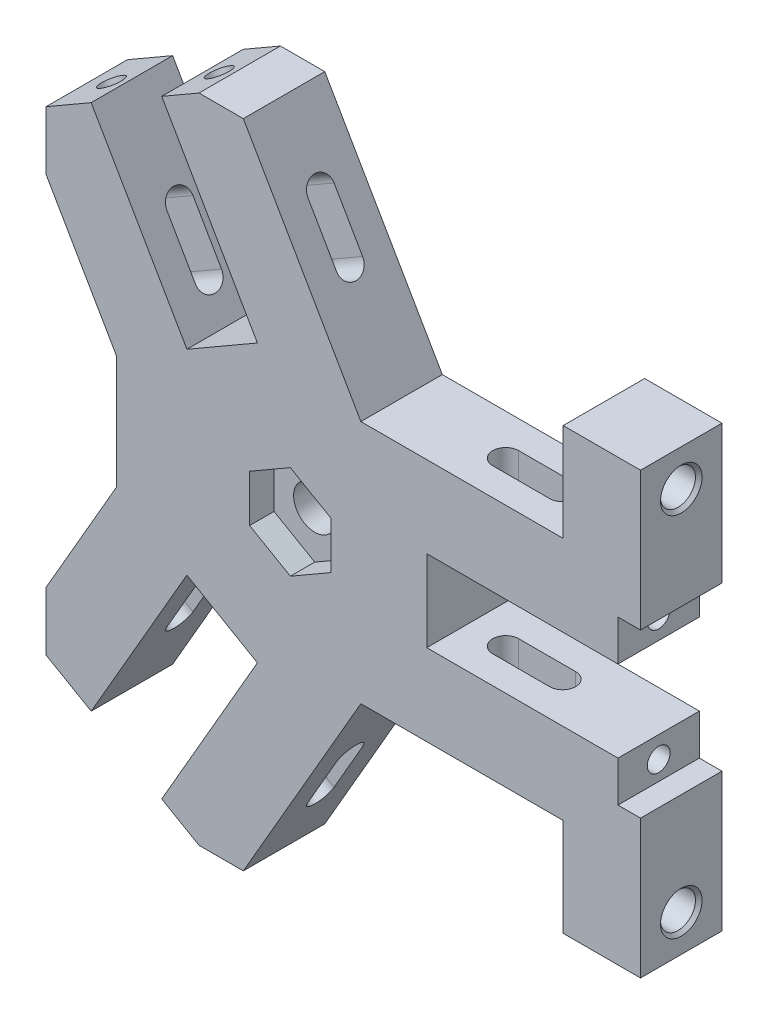
SolidWorks part; units mm, degrees
ref_plane "Front" through (0, 0, 0) normal (0, 0, 1) x (1, 0, 0)
ref_plane "Top" through (0, 0, 0) normal (0, 1, 0) x (1, 0, 0)
ref_plane "Right" through (0, 0, 0) normal (1, 0, 0) x (0, 0, -1)
sketch "Sketch1" plane through (0, 0, 0) normal (0, 0, 1) x (1, 0, 0)
  line L1 (0, 0) -> (73, 0)
  line L2 (0, 0) -> (0, 80)
  line L3 (0, 80) -> (73, 80)
  line L4 (73, 0) -> (73, 80)
  dimension "D1" = 80
  dimension "D2" = 73
extrude "Boss-Extrude1" add sketch "Sketch1" along normal blind 10
sketch "Sketch2" plane through (0, 0, 10) normal (0, 0, 1) x (1, 0, 0)
  line L1 (0, 80) -> (0, 0) construction
  line L2 (18.75, 59.4856) -> (18.75, 20.5144) construction
  line L3 (18.75, 20.5144) -> (52.5, 40) construction
  line L4 (52.5, 40) -> (18.75, 59.4856) construction
  circle A0 centre (30, 40) radius 22.5 construction
  point P3 (0, 40)
  dimension "D1" = 22.5
  dimension "D3" = 30
ref_axis "Axis1" through (30, 40, 10) along (0, 0, -1)
sketch "Sketch3" plane through (0, 0, 10) normal (0, 0, 1) x (1, 0, 0)
  line L0 (25.9551, 57.0059) -> (17.2949, 52.0059)
  line L1 (25.9551, 57.0059) -> (20.2051, 66.9652)
  line L2 (17.2949, 52.0059) -> (11.5449, 61.9652)
  line L3 (20.2051, 66.9652) -> (11.5449, 61.9652)
  line L4 (25.9551, 57.0059) -> (11.5449, 61.9652) construction
  line L5 (17.2949, 52.0059) -> (20.2051, 66.9652) construction
  line L6 (11.5449, 18.0348) -> (20.2051, 13.0348)
  line L7 (11.5449, 18.0348) -> (17.2949, 27.9941)
  line L8 (20.2051, 13.0348) -> (25.9551, 22.9941)
  line L9 (17.2949, 27.9941) -> (25.9551, 22.9941)
  line L10 (11.5449, 18.0348) -> (25.9551, 22.9941) construction
  line L11 (20.2051, 13.0348) -> (17.2949, 27.9941) construction
  line L13 (46.75, 45) -> (58.25, 45)
  line L14 (46.75, 45) -> (46.75, 35)
  line L15 (46.75, 35) -> (58.25, 35)
  line L16 (58.25, 45) -> (58.25, 35)
  line L17 (46.75, 45) -> (58.25, 35) construction
  line L18 (46.75, 35) -> (58.25, 45) construction
  point P0 (52.5, 40)
  point P1 (18.75, 59.4856)
  point P2 (18.75, 20.5144)
  dimension "D1" = 60
  dimension "D2" = 60
  dimension "D3" = 10
  dimension "D4" = 10
  dimension "D5" = 10
  dimension "D6" = 11.5
  dimension "D7" = 11.5
  dimension "D8" = 11.5
extrude "Cut-Extrude1" cut sketch "Sketch3" against normal blind 10
sketch "Sketch4" plane through (0, 45, 0) normal (0, -1, 0) x (1, 0, 0)
  line L0 (52.5, 7.2) -> (73, 7.2)
  line L1 (73, 10) -> (73, 0) construction
  line L2 (73, 7.2) -> (73, 2.8)
  line L3 (73, 2.8) -> (52.5, 2.8)
  line L4 (58.25, 10) -> (46.75, 10) construction
  arc A0 (52.5, 2.8) -> (52.5, 7.2) centre (52.5, 5) cw
  point P10 (52.5, 10)
  dimension "D1" = 2.2
  dimension "D2" = 5
sketch "Sketch5" plane through (0, 0, 10) normal (0, 0, 1) x (1, 0, 0)
  line L1 (58.25, 45) -> (85.6587, 45)
  line L2 (58.25, 45) -> (58.25, 35)
  line L3 (58.25, 35) -> (85.6587, 35)
  line L4 (85.6587, 45) -> (85.6587, 35)
extrude "Cut-Extrude3" cut sketch "Sketch5" against normal blind 10
sketch "Sketch6" plane through (9.5096, -5.4904, 0) normal (-0.866, 0.5, 0) x (0, 0, 1)
  line L0 (2.8, 27.141) -> (2.8, -15.6837)
  line L1 (2.8, -15.6837) -> (7.2, -15.6837)
  line L2 (7.2, -15.6837) -> (7.2, 27.141)
  line L3 (10, 21.391) -> (10, 32.891) construction
  arc A0 (2.8, 27.141) -> (7.2, 27.141) centre (5, 27.141) cw
  point P8 (10, 27.141)
  dimension "D1" = 2.2
  dimension "D2" = 5
  dimension "D3" = 4.4
pattern_circular "CirPattern1" count 3 over 360 about axis through (30, 40, 10) along (0, 0, -1) of "Cut-Extrude3"
ref_plane "Plane1" through (39.8205, 22.9904, 0) normal (0.866, 0.5, 0) x (0, 0, -1)
ref_plane "Plane2" through (5.1795, -2.9904, 0) normal (-0.866, 0.5, 0) x (0, 0, -1)
sketch "Sketch7" plane through (44.1506, 25.4904, 0) normal (-0.866, -0.5, 0) x (0, 0, 1)
  line L0 (2.8, 42.141) -> (2.8, 92.141)
  line L1 (2.8, 92.141) -> (7.2, 92.141)
  line L2 (7.2, 92.141) -> (7.2, 42.141)
  line L3 (10, 36.391) -> (10, 62.9423) construction
  arc A0 (2.8, 42.141) -> (7.2, 42.141) centre (5, 42.141) ccw
  dimension "D1" = 2.2
  dimension "D2" = 5
  dimension "D3" = 4.4
  dimension "D4" = 50
hole_wizard "M6 Clearance Hole1" positions "Sketch8" profile "Sketch9" hole size "M6" standard "ISO" end condition through all
sketch "Sketch8" plane through (0, 0, 10) normal (0, 0, 1) x (1, 0, 0)
  point P0 (30, 40)
sketch "Sketch9" plane through (30, 40, 10) normal (1, 0, 0) x (0, -1, 0)
  line L0 (0, 0) -> (0, 10)
  line L1 (0, 10) -> (2.6, 10)
  line L2 (2.6, 10) -> (2.6, 0)
  line L5 (2.6, 0) -> (0, 0)
  line L11 (0, -6.35) -> (0, 107.95) construction
  dimension "Thru Hole Dia." = 5.2
  dimension "Thru Hole Depth" = 10
sketch "Sketch10" plane through (0, 0, 10) normal (0, 0, 1) x (1, 0, 0)
  line L0 (17.2949, 52.0059) -> (25.9551, 57.0059) construction
  line L1 (30, 45.7735) -> (25, 42.8868)
  line L2 (25, 42.8868) -> (25, 37.1132)
  line L3 (25, 37.1132) -> (30, 34.2265)
  line L4 (30, 34.2265) -> (35, 37.1132)
  line L5 (35, 37.1132) -> (35, 42.8868)
  line L6 (35, 42.8868) -> (30, 45.7735)
  circle A0 centre (30, 40) radius 5 construction
  dimension "D1" = 10
extrude "Cut-Extrude6" cut sketch "Sketch10" against normal blind 3
ref_axis "Axis2" through (30, 40, 0) along (0, 0, 1)
ref_plane "Plane4" through (30, 0, 0) normal (-1, 0, 0) x (0, 0, 1)
sketch "Sketch11" plane through (0, 0, 0) normal (0, -1, 0) x (1, 0, 0)
  line L0 (73, 10) -> (73, 0) construction
  line L1 (51.44, 6.6) -> (58.44, 6.6)
  line L2 (51.44, 3.4) -> (58.44, 3.4)
  line L3 (12.6795, 10) -> (73, 10) construction
  arc A1 (51.44, 6.6) -> (51.44, 3.4) centre (51.44, 5) ccw
  arc A2 (58.44, 6.6) -> (58.44, 3.4) centre (58.44, 5) cw
  dimension "D1" = 1.6
  dimension "D4" = 5
  dimension "D2" = 7
  dimension "D3" = 14.56
extrude "Cut-Extrude7" cut sketch "Sketch11" against normal through all
pattern_circular "CirPattern2" count 3 over 360 about axis through (30, 40, 7) along (0, 0, -1) of "Cut-Extrude7"
sketch "Sketch12" plane through (0, 0, 10) normal (0, 0, 1) x (1, 0, 0)
  line L0 (73, 0) -> (73, 25)
  line L1 (73, 0) -> (73, 35) construction
  line L2 (73, 25) -> (38.6603, 25)
  line L3 (38.6603, 25) -> (24.2265, 0)
  line L4 (12.6795, 0) -> (73, 0) construction
  line L5 (24.2265, 0) -> (73, 0)
  line L6 (12.6795, 0) -> (25.9551, 22.9941) construction
  line L8 (46.75, 35) -> (73, 35) construction
  dimension "D1" = 10
  dimension "D2" = 10
extrude "Cut-Extrude8" cut sketch "Sketch12" against normal blind 10
ref_plane "Plane3" through (0, 40, 0) normal (0, -1, 0) x (-1, 0, 0)
mirror "Mirror1" about plane through (0, 40, 0) normal (0, -1, 0) of "Cut-Extrude8"
sketch "Sketch13" plane through (0, 0, 10) normal (0, 0, 1) x (1, 0, 0)
  line L0 (0, 61.9615) -> (8.6244, 47.0237)
  line L1 (0, 80) -> (0, 0) construction
  line L2 (8.6244, 47.0237) -> (8.6244, 32.9763)
  line L3 (8.6244, 32.9763) -> (0, 18.0385)
  line L4 (0, 18.0385) -> (0, 61.9615)
  line L5 (1.1325, 80) -> (17.2949, 52.0059) construction
  line L6 (17.2949, 27.9941) -> (1.1325, 0) construction
  circle A0 centre (30, 40) radius 22.5 construction
  dimension "D1" = 10
extrude "Cut-Extrude9" cut sketch "Sketch13" against normal blind 10
sketch "Sketch14" plane through (0, 0, 10) normal (0, 0, 1) x (1, 0, 0)
  line L0 (-3.1154, 12.6425) -> (22.8654, -2.3575)
  line L1 (22.8654, -2.3575) -> (18.1699, -10.4904)
  line L2 (18.1699, -10.4904) -> (-7.8109, 4.5096)
  line L3 (-7.8109, 4.5096) -> (-3.1154, 12.6425)
  line L4 (25.9551, 22.9941) -> (17.2949, 27.9941) construction
  line L5 (38.6603, 25) -> (24.2265, 0) construction
  line L6 (0, 18.0385) -> (8.6244, 32.9763) construction
  dimension "D1" = 23.5
extrude "Cut-Extrude10" cut sketch "Sketch14" against normal blind 10
mirror "Mirror2" about plane through (0, 40, 0) normal (0, -1, 0) of "Cut-Extrude10"
sketch "Sketch15" plane through (0, 0, 10) normal (0, 0, 1) x (1, 0, 0)
  line L0 (73, 45) -> (73, 55) construction
  line L1 (73, 19) -> (182, 19)
  line L2 (73, 19) -> (73, 61)
  line L3 (73, 61) -> (182, 61)
  line L4 (182, 19) -> (182, 61)
  line L5 (0, 0) -> (0, 81.4596) construction
  point P6 (73, 40)
  dimension "D1" = 42
  dimension "D2" = 182
extrude "Boss-Extrude2" add sketch "Sketch15" against normal blind 10
sketch "Sketch16" plane through (0, 0, 10) normal (0, 0, 1) x (1, 0, 0)
  line L1 (73, 50.5) -> (98, 50.5)
  line L2 (73, 50.5) -> (73, 29.5)
  line L3 (73, 29.5) -> (98, 29.5)
  line L4 (98, 50.5) -> (98, 29.5)
  line L5 (73, 45) -> (73, 35) construction
  line L7 (182, 61) -> (73, 61) construction
  dimension "D1" = 25
  dimension "D2" = 21
  dimension "D3" = 10.5
sketch "Sketch18" plane through (0, 0, 10) normal (0, 0, 1) x (1, 0, 0)
  line L0 (182, 61) -> (73, 61) construction
  line L1 (113.8, 24.5) -> (82.8, 24.5)
  line L2 (113.8, 24.5) -> (113.8, 55.5)
  line L3 (113.8, 55.5) -> (82.8, 55.5)
  line L4 (82.8, 24.5) -> (82.8, 55.5)
  line L5 (113.8, 24.5) -> (82.8, 55.5) construction
  line L6 (113.8, 55.5) -> (82.8, 24.5) construction
  line L7 (73, 61) -> (73, 55) construction
  point P0 (98.3, 40)
  dimension "D1" = 31
  dimension "D2" = 31
  dimension "D3" = 68.3
  dimension "D4" = 5.5
  dimension "D5" = 9.8
sketch "Sketch21" plane through (0, 0, 10) normal (0, 0, 1) x (1, 0, 0)
  line L4 (97.55, 40) -> (99.05, 40) construction
  line L5 (113.8, 24.5) -> (82.8, 55.5) construction
  line L6 (97.55, 47.5) -> (99.05, 47.5)
  line L7 (97.55, 32.5) -> (99.05, 32.5)
  arc A2 (97.55, 47.5) -> (97.55, 32.5) centre (97.55, 40) ccw
  arc A3 (99.05, 32.5) -> (99.05, 47.5) centre (99.05, 40) ccw
  point P5 (98.3, 40)
  dimension "D1" = 15
  dimension "D2" = 1.5
sketch "Sketch22" plane through (0, 0, 10) normal (0, 0, 1) x (1, 0, 0)
  line L0 (182, 19) -> (182, 61) construction
  line L1 (182, 67) -> (167, 67)
  line L2 (182, 67) -> (182, 13)
  line L3 (182, 13) -> (167, 13)
  line L4 (167, 67) -> (167, 13)
  point P6 (182, 40)
  dimension "D1" = 15
  dimension "D2" = 54
extrude "Boss-Extrude3" add sketch "Sketch22" against normal blind 10
sketch "Sketch23" plane through (182, 0, 0) normal (1, 0, 0) x (0, 0, -1)
  line L0 (-5, 62.5) -> (-5, 17.5) construction
  point P2 (-5, 40)
  dimension "D1" = 45
  dimension "D2" = 5
hole_wizard "M4 Clearance Hole1" positions "Sketch24" profile "Sketch25" hole size "M4" standard "DIN"
sketch "Sketch24" plane through (182, 0, 0) normal (1, 0, 0) x (0, 0, -1)
  point P0 (-5, 62.5)
  point P3 (-5, 17.5)
sketch "Sketch25" plane through (182, 62.5, 5) normal (0, 1, 0) x (0, 0, -1)
  line L0 (0, 0) -> (0, 31.3519)
  line L1 (0, 31.3519) -> (2.25, 30)
  line L2 (2.25, 30) -> (2.25, 0)
  line L5 (2.25, 0) -> (0, 0)
  line L10 (0, 31.3519) -> (-2.25, 30) construction
  line L11 (0, -6.35) -> (0, 107.95) construction
  dimension "Hole Dia." = 4.5
  dimension "Hole Depth" = 30
  dimension "Drill Angle" = 118
sketch "Sketch26" plane through (0, 0, 10) normal (0, 0, 1) x (1, 0, 0)
  line L0 (119.3, 61) -> (119.3, 55)
  line L1 (167, 61) -> (73, 61) construction
  line L2 (119.3, 55) -> (167, 55)
  line L3 (167, 55) -> (167, 61)
  line L4 (167, 61) -> (119.3, 61)
  dimension "D1" = 5.5
  dimension "D2" = 6
extrude "Cut-Extrude13" cut sketch "Sketch26" against normal blind 10
mirror "Mirror3" about plane through (0, 40, 0) normal (0, -1, 0) of "Cut-Extrude13"
chamfer "Chamfer1" distance 4 angle 60 2 edges at (119.3, 25, 5) (119.3, 55, 5) first distance on face at (143.15, 25, 5) first distance on face at (143.15, 55, 5)
sketch "Sketch27" plane through (0, 0, 10) normal (0, 0, 1) x (1, 0, 0)
  line L1 (73, 61) -> (77.3, 61)
  line L2 (73, 61) -> (73, 55)
  line L3 (73, 55) -> (77.3, 55)
  line L4 (77.3, 61) -> (77.3, 55)
  dimension "D1" = 6
  dimension "D2" = 5.5
extrude "Cut-Extrude14" cut sketch "Sketch27" against normal blind 10
mirror "Mirror4" about plane through (0, 40, 0) normal (0, -1, 0) of "Cut-Extrude14"
chamfer "Chamfer2" distance 4 angle 60 2 edges at (77.3, 55, 5) (77.3, 25, 5) first distance on face at (57.9801, 55, 5) first distance on face at (57.9801, 25, 5)
extrude "Cut-Extrude15" cut sketch "Sketch21" against normal blind 10
sketch "Sketch28" plane through (0, 0, 10) normal (0, 0, 1) x (1, 0, 0)
  line L0 (97.55, 40) -> (99.05, 40) construction
  line L1 (97.55, 51.25) -> (99.05, 51.25)
  line L2 (97.55, 28.75) -> (99.05, 28.75)
  circle A0 centre (98.3, 40) radius 11 construction
  arc A1 (97.55, 51.25) -> (97.55, 28.75) centre (97.55, 40) ccw
  arc A2 (99.05, 28.75) -> (99.05, 51.25) centre (99.05, 40) ccw
  point P5 (98.3, 40)
  dimension "D1" = 22
  dimension "D2" = 11.25
  dimension "D3" = 1.5
extrude "Cut-Extrude16" cut sketch "Sketch28" against normal blind 2.2
sketch "Sketch29" plane through (0, 0, 10) normal (0, 0, 1) x (1, 0, 0)
  line L0 (82.05, 55.5) -> (83.55, 55.5) construction
  line L1 (113.8, 55.5) -> (82.8, 55.5) construction
  line L2 (82.05, 57.2) -> (83.55, 57.2)
  line L3 (82.05, 53.8) -> (83.55, 53.8)
  line L4 (113.05, 53.8) -> (114.55, 53.8)
  line L5 (113.05, 57.2) -> (114.55, 57.2)
  line L6 (113.05, 55.5) -> (114.55, 55.5) construction
  line L7 (113.05, 22.8) -> (114.55, 22.8)
  line L8 (113.05, 26.2) -> (114.55, 26.2)
  line L9 (113.05, 24.5) -> (114.55, 24.5) construction
  line L10 (82.05, 22.8) -> (83.55, 22.8)
  line L11 (82.05, 26.2) -> (83.55, 26.2)
  line L12 (82.05, 24.5) -> (83.55, 24.5) construction
  arc A0 (82.05, 57.2) -> (82.05, 53.8) centre (82.05, 55.5) ccw
  arc A1 (83.55, 53.8) -> (83.55, 57.2) centre (83.55, 55.5) ccw
  arc A2 (113.05, 57.2) -> (113.05, 53.8) centre (113.05, 55.5) ccw
  arc A3 (114.55, 53.8) -> (114.55, 57.2) centre (114.55, 55.5) ccw
  arc A4 (113.05, 26.2) -> (113.05, 22.8) centre (113.05, 24.5) ccw
  arc A5 (114.55, 22.8) -> (114.55, 26.2) centre (114.55, 24.5) ccw
  arc A6 (82.05, 26.2) -> (82.05, 22.8) centre (82.05, 24.5) ccw
  arc A7 (83.55, 22.8) -> (83.55, 26.2) centre (83.55, 24.5) ccw
  point P5 (82.8, 55.5)
  point P15 (113.8, 55.5)
  point P22 (113.8, 24.5)
  point P29 (82.8, 24.5)
  dimension "D1" = 3.4
  dimension "D2" = 1.5
  dimension "D3" = 2
  dimension "D4" = 2
extrude "Cut-Extrude17" cut sketch "Sketch29" against normal blind 10
sketch "Sketch30" plane through (0, 0, 10) normal (0, 0, 1) x (1, 0, 0)
  line L0 (167, 67) -> (167, 55) construction
  line L1 (134, 29.5) -> (155, 29.5) construction
  line L2 (134, 29.5) -> (134, 50.5) construction
  line L3 (134, 50.5) -> (155, 50.5) construction
  line L4 (155, 29.5) -> (155, 50.5) construction
  line L6 (123.3, 55) -> (167, 55) construction
  dimension "D1" = 21
  dimension "D2" = 21
  dimension "D3" = 12
  dimension "D4" = 4.5
hole_wizard "M4 Clearance Hole2" positions "Sketch31" profile "Sketch32" hole size "M4" standard "DIN" end condition through all
sketch "Sketch31" plane through (0, 0, 10) normal (0, 0, 1) x (1, 0, 0)
  point P0 (134, 50.5)
  point P3 (155, 50.5)
  point P6 (155, 29.5)
  point P9 (134, 29.5)
sketch "Sketch32" plane through (134, 50.5, 10) normal (1, 0, 0) x (0, -1, 0)
  line L0 (0, 0) -> (0, 10)
  line L1 (0, 10) -> (2.25, 10)
  line L2 (2.25, 10) -> (2.25, 0)
  line L5 (2.25, 0) -> (0, 0)
  line L11 (0, -6.35) -> (0, 107.95) construction
  dimension "Thru Hole Dia." = 4.5
  dimension "Thru Hole Depth" = 10
sketch "Sketch33" plane through (73, 0, 0) normal (-1, 0, 0) x (0, 0, 1)
  line L1 (-10, 85) -> (20, 85)
  line L2 (-10, 85) -> (-10, -5)
  line L3 (-10, -5) -> (20, -5)
  line L4 (20, 85) -> (20, -5)
  dimension "D1" = 10
  dimension "D2" = 30
  dimension "D3" = 90
  dimension "D4" = 5
extrude "Cut-Extrude18" cut sketch "Sketch33" against normal through all contours L4 L3 L2 L1
sketch "Sketch34" plane through (73, 0, 0) normal (1, 0, 0) x (0, 0, -1)
  line L5 (0, 45) -> (0, 67)
  line L6 (0, 67) -> (-10, 67)
  line L7 (-10, 67) -> (-10, 45)
  line L8 (0, 45) -> (0, 35) construction
  line L9 (-10, 45) -> (0, 45)
  point P18 (0, 40)
  dimension "D1" = 27
  dimension "D2" = 22
  dimension "D3" = 10
  dimension "D4" = 10
extrude "Boss-Extrude4" add sketch "Sketch34" against normal blind 9.5
mirror "Mirror5" about plane through (0, 40, 0) normal (0, -1, 0) of "Boss-Extrude4"
sketch "Sketch35" plane through (73, 0, 0) normal (1, 0, 0) x (0, 0, -1)
  line L0 (-5, 62.5) -> (-5, 17.5)
  line L1 (-10, 67) -> (-10, 45) construction
  line L2 (0, 67) -> (-10, 67) construction
  dimension "D1" = 45
  dimension "D2" = 5
  dimension "D3" = 4.5
sketch "Sketch38" plane through (73, 0, 0) normal (1, 0, 0) x (0, 0, -1)
  circle A0 centre (-5, 62.5) radius 2.15
  circle A1 centre (-5, 17.5) radius 2.15
  dimension "D1" = 4.3
  dimension "D2" = 4.3
extrude "Cut-Extrude20" cut sketch "Sketch38" against normal blind 21
chamfer "Chamfer7" distance 0.4 angle 45 1 edges at (32.6, 40, 0)
chamfer "Chamfer9" distance 0.4 angle 45 4 edges at (63.5, 17.5, 2.85) (73, 17.5, 2.85) (63.5, 62.5, 2.85) (73, 62.5, 2.85)
sketch "Sketch57" plane through (-29.9455, 51.8671, 0) normal (-0.5, 0.866, 0) x (0.866, 0.5, 0)
  line L1 (40.9808, -10) -> (40.9808, 0) construction
  line L8 (45.9808, 0) -> (45.9808, -10)
  circle A0 centre (38.3408, -5.2258) radius 1.4
  circle A1 centre (53.6208, -5.2258) radius 1.4
  dimension "D1" = 2.64
extrude "Cut-Extrude21" cut sketch "Sketch57" against normal blind 5 contours A0 | A1
sketch "Sketch58" plane through (4.6955, 8.1329, 0) normal (-0.5, -0.866, 0) x (-0.866, 0.5, 0)
  line L0 (-0.9808, -10) -> (-0.9808, 0) construction
  line L1 (-0.9808, -10) -> (-10.9808, -10)
  line L2 (-0.9808, 0) -> (-10.9808, 0)
  line L3 (-5.9808, -10) -> (-5.9808, 0)
  circle A0 centre (1.6592, -5) radius 1.4
  circle A1 centre (-13.6208, -5) radius 1.4
  point P4 (-0.9808, -5)
  dimension "D1" = 2.64
extrude "Cut-Extrude22" cut sketch "Sketch58" against normal blind 5 contours A0 | A1
sketch "Sketch59" plane through (0, 0, 10) normal (0, 0, 1) x (1, 0, 0)
  line L0 (73, 50) -> (70.2271, 50)
  line L1 (73, 67) -> (73, 45) construction
  line L2 (70.2271, 50) -> (70.2271, 30)
  line L3 (70.2271, 30) -> (73, 30)
  line L4 (73, 35) -> (73, 13) construction
  line L5 (73, 30) -> (73, 50)
  line L7 (63.5, 25) -> (38.6603, 25) construction
  line L8 (63.5, 55) -> (38.6603, 55) construction
  point P12 (71.6136, 30)
  dimension "D1" = 5
  dimension "D2" = 5
extrude "Cut-Extrude23" cut sketch "Sketch59" against normal blind 10
sketch "Sketch60" plane through (70.2271, 0, 0) normal (1, 0, 0) x (0, 0, -1)
  line L0 (-10, 45) -> (-10, 35)
  line L1 (-10, 35) -> (-10, 30) construction
  line L2 (-10, 35) -> (0, 35) construction
  line L3 (0, 45) -> (0, 35)
  line L4 (-10, 40) -> (0, 40)
  circle A0 centre (-5, 32.36) radius 1.4
  circle A1 centre (-5, 47.64) radius 1.4
  point P15 (-5, 35)
  dimension "D1" = 2.64
extrude "Cut-Extrude24" cut sketch "Sketch60" against normal blind 5 contours A0 | A1
